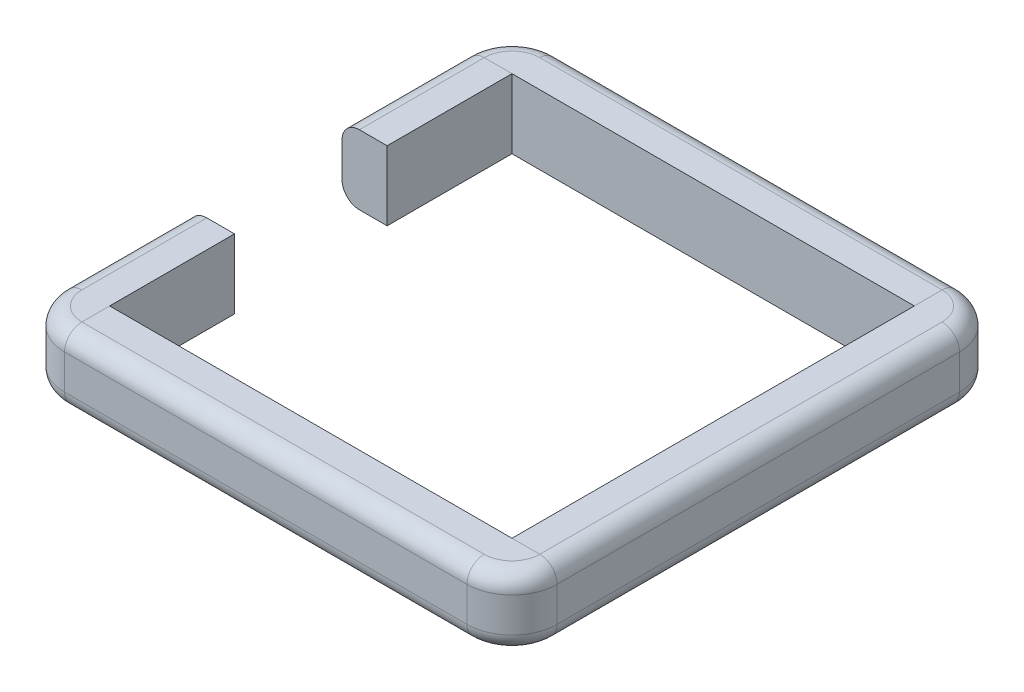
SolidWorks part; units mm, degrees
ref_plane "Front Plane" through (0, 0, 0) normal (0, 0, 1) x (1, 0, 0)
ref_plane "Top Plane" through (0, 0, 0) normal (0, 1, 0) x (1, 0, 0)
ref_plane "Right Plane" through (0, 0, 0) normal (1, 0, 0) x (0, 0, -1)
sketch "Sketch1" plane through (0, 0, 0) normal (0, 0, 1) x (1, 0, 0)
  line L0 (31.75, 31.75) -> (0, 31.75)
  line L1 (31.75, -95.25) -> (50.8, -95.25)
  line L2 (31.75, -95.25) -> (31.75, 31.75)
  line L3 (31.75, 31.75) -> (50.8, 31.75)
  line L4 (50.8, -95.25) -> (50.8, 31.75)
  line L5 (-31.75, 0) -> (-31.75, -63.5)
  line L6 (0, -95.25) -> (31.75, -95.25)
  circle A0 centre (0, 0) radius 31.75
  circle A1 centre (0, -63.5) radius 31.75
  dimension "D1" = 63.5
  dimension "D2" = 19.05
extrude "Boss-Extrude1" add sketch "Sketch1" along normal blind 736.6 contours A0 L2 L0 | A0 | A1 A0 L5 | A1 | A1 L2 A0 | L1 L4 L3 L2 | A1 L6 L2 region at (24.6581, 24.6581, 0) region at (41.275, -31.75, 0) region at (0, 0, 0) region at (24.6581, -31.75, 0) region at (-24.6581, -31.75, 0) region at (24.6581, -88.1581, 0) region at (0, -63.5, 0)
sketch "Sketch2" plane through (0, 0, 736.6) normal (0, 0, 1) x (1, 0, 0)
  line L4 (-31.75, 0) -> (-31.75, -63.5)
  line L5 (0, -95.25) -> (50.8, -95.25)
  line L6 (50.8, -95.25) -> (50.8, 31.75)
  line L7 (50.8, 31.75) -> (0, 31.75)
  line L8 (-31.75, 0) -> (-31.75, -63.5)
  line L9 (0, -95.25) -> (50.8, -95.25)
  line L10 (50.8, -95.25) -> (50.8, 31.75)
  line L11 (50.8, 31.75) -> (0, 31.75)
  arc A2 (-31.75, -63.5) -> (0, -95.25) centre (0, -63.5) ccw
  arc A3 (0, 31.75) -> (-31.75, 0) centre (0, 0) ccw
  arc A4 (-31.75, -63.5) -> (0, -95.25) centre (0, -63.5) ccw
  arc A5 (0, 31.75) -> (-31.75, 0) centre (0, 0) ccw
  dimension "D1" = 0
revolve "Revolve1" add sketch "Sketch2" angle 90 about L10
sketch "Sketch3" plane through (0, 31.75, 0) normal (0, 1, 0) x (1, 0, 0)
  line L1 (50.8, 0) -> (787.4, 0)
  line L2 (50.8, 0) -> (50.8, -736.6)
  line L3 (50.8, -736.6) -> (787.4, -736.6)
  line L4 (787.4, 0) -> (787.4, -736.6)
  circle A0 centre (419.1, -368.3) radius 51.1526
  point P5 (419.1, -368.3)
  dimension "D1" = 736.6
sketch "Sketch4" plane through (0, -95.25, 0) normal (0, -1, 0) x (-1, 0, 0)
  point P0 (-419.1, -368.3)
ref_axis "Axis1" through (419.1, -95.25, 368.3) along (0, 1, 0)
pattern_circular "CirPattern1" count 4 every 90 about axis through (419.1, -95.25, 368.3) along (0, 1, 0) of bodies 102
sketch "Sketch5" plane through (0, 31.75, 0) normal (0, 1, 0) x (1, 0, 0)
  line L0 (50.8, -787.4) -> (50.8, 0) construction
  line L1 (50.8, -508) -> (-84.0173, -508)
  line L2 (50.8, -508) -> (50.8, -228.6)
  line L3 (50.8, -228.6) -> (-84.0173, -228.6)
  line L4 (-84.0173, -508) -> (-84.0173, -228.6)
  line L5 (50.8, -508) -> (-84.0173, -228.6) construction
  line L6 (50.8, -228.6) -> (-84.0173, -508) construction
  line L8 (0, 0) -> (787.4, 0) construction
  point P4 (-16.6086, -368.3)
  dimension "D1" = 368.3
  dimension "D2" = 279.4
extrude "Cut-Extrude1" cut sketch "Sketch5" against normal through all
